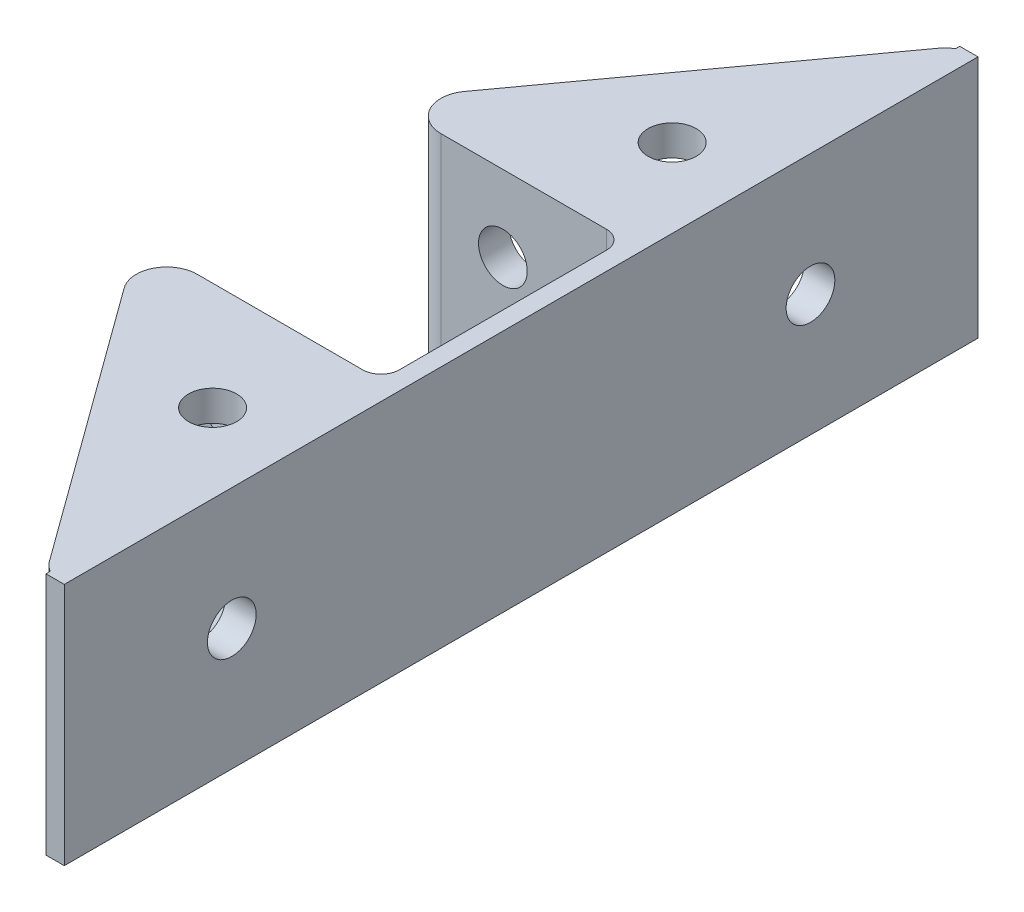
SolidWorks part; units mm, degrees
ref_plane "Front Plane" through (0, 0, 0) normal (0, 0, 1) x (1, 0, 0)
ref_plane "Top Plane" through (0, 0, 0) normal (0, 1, 0) x (1, 0, 0)
ref_plane "Right Plane" through (0, 0, 0) normal (1, 0, 0) x (0, 0, -1)
sketch "Sketch2" plane through (23, 0, 0) normal (-1, 0, 0) x (0, 0, 1)
  line L1 (-95, 0) -> (55, 0)
  line L2 (-95, 0) -> (-95, 40)
  line L3 (-95, 40) -> (55, 40)
  line L4 (55, 0) -> (55, 40)
  line L5 (-95, 0) -> (55, 40) construction
  line L6 (-95, 40) -> (55, 0) construction
  point P4 (-20, 20)
extrude "Boss-Extrude1" add sketch "Sketch2" along normal up to surface (3 mm away)
sketch "Sketch3" plane through (0, 0, 0) normal (0, -1, 0) x (1, 0, 0)
  line L0 (20, 55) -> (-20, 0)
  line L1 (-20, 0) -> (20, 0)
  line L2 (20, -95) -> (20, 55) construction
  line L3 (20, 0) -> (20, 55)
  line L4 (-20, -35) -> (-20, -5) construction
extrude "Boss-Extrude2" add sketch "Sketch3" against normal up to surface (40 mm away)
shell "Shell3" thickness 5 removed face at (0, 20, 27.5)
fillet "Fillet2" radius 5 2 edges at (20, 20, 55) (-20, 20, 0)
hole_wizard "Ø8.0mm Dowel Hole1" positions "Sketch4" profile "Sketch5" hole size "Ø8.0" standard "ISO" end condition up to next
sketch "Sketch4" plane through (0, 0, 5) normal (0, 0, 1) x (1, 0, 0)
  line L0 (0, 27.5) -> (0, 12.5) construction
  line L2 (0, 20) -> (16.3636, 20) construction
  line L3 (16.3636, 5) -> (16.3636, 35) construction
  line L6 (-15, 250) -> (15, 250) construction
  point P0 (0, 12.5)
  point P2 (0, 27.5)
  point P23 (0, 250)
  point P24 (0, 14.1897)
  dimension "D1" = 15
sketch "Sketch5" plane through (0, 12.5, 5) normal (1, 0, 0) x (0, -1, 0)
  line L0 (0, 0) -> (0, 5)
  line L1 (0, 5) -> (4, 5)
  line L2 (4, 5) -> (4, 0)
  line L5 (4, 0) -> (0, 0)
  line L11 (0, -6.35) -> (0, 107.95) construction
  dimension "Thru Hole Dia." = 8
  dimension "Thru Hole Depth" = 5
hole_wizard "Ø8.0mm Dowel Hole2" positions "Sketch6" profile "Sketch7" hole size "Ø8.0" standard "ISO"
sketch "Sketch6" plane through (18, 0, 0) normal (-1, 0, 0) x (0, 0, 1)
  line L0 (50, 35) -> (5, 35) construction
  line L1 (50, 5) -> (50, 35) construction
  point P0 (27.5, 20)
  point P8 (27.5, 35)
  point P11 (50, 20)
sketch "Sketch7" plane through (18, 20, 27.5) normal (0, 1, 0) x (0, 0, 1)
  line L0 (0, 0) -> (0, 7.4034)
  line L1 (0, 7.4034) -> (4, 5)
  line L2 (4, 5) -> (4, 0)
  line L5 (4, 0) -> (0, 0)
  line L10 (0, 7.4034) -> (-4, 5) construction
  line L11 (0, -6.35) -> (0, 107.95) construction
  dimension "Hole Dia." = 8
  dimension "Hole Depth" = 5
  dimension "Drill Angle" = 118
ref_plane "Plane1" through (0, 0, -20) normal (0, 0, 1) x (1, 0, 0)
sketch "Sketch8" plane through (0, 35, 0) normal (0, -1, 0) x (1, 0, 0)
  line L0 (2.1388, 30.4409) -> (18, 5) construction
  line L1 (18.5024, 52.9409) -> (-14.2248, 7.9409) construction
  circle A0 centre (10.0694, 17.7204) radius 3.95
  dimension "D1" = 7.9
extrude "Cut-Extrude1" cut sketch "Sketch8" against normal up to next
mirror "Mirror2" about plane through (0, 0, -20) normal (0, 0, 1) of bodies 107 104
fillet "Fillet3" radius 3 2 edges at (20, 20, 0) (20, 20, -40)
sketch "Sketch9" plane through (20, 0, 0) normal (-1, 0, 0) x (0, 0, 1)
  circle A1 centre (27.5, 20) radius 4
  circle A2 centre (27.5, 20) radius 4
  circle A3 centre (-67.5, 20) radius 4
  circle A4 centre (-67.5, 20) radius 4
  dimension "D1" = 0
  dimension "D2" = 0
extrude "Cut-Extrude2" cut sketch "Sketch9" against normal up to next
